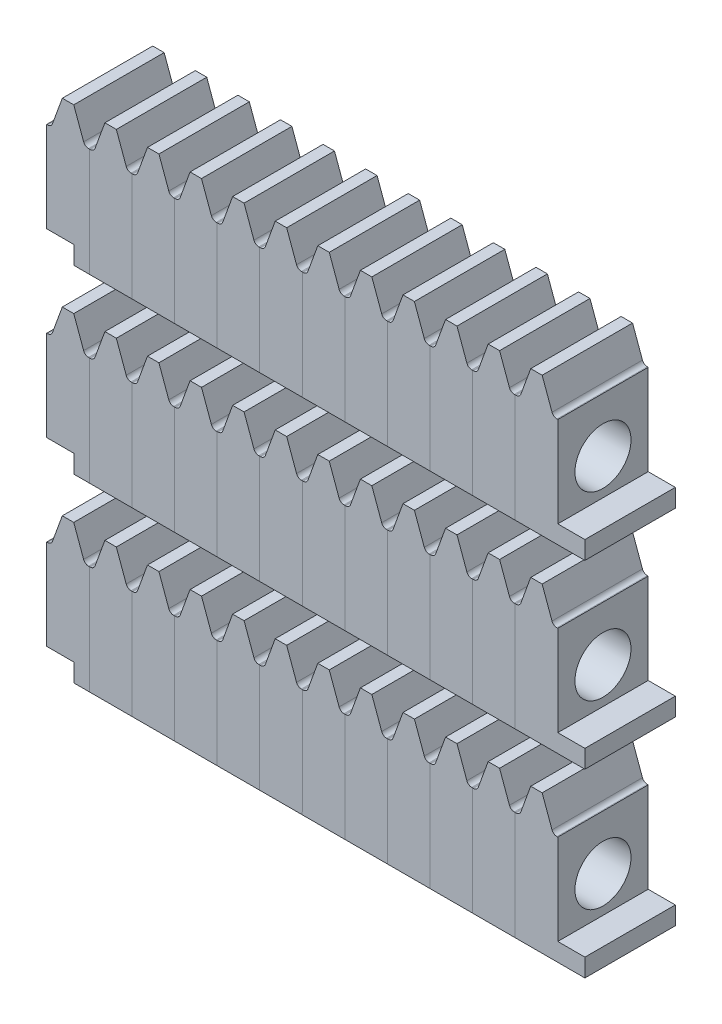
SolidWorks part; units mm, degrees
ref_plane "Front Plane" through (0, 0, 0) normal (0, 0, 1) x (1, 0, 0)
ref_plane "Top Plane" through (0, 0, 0) normal (0, 1, 0) x (1, 0, 0)
ref_plane "Right Plane" through (0, 0, 0) normal (1, 0, 0) x (0, 0, -1)
ref_axis "Axis1" through (0.1856, 0, 0) along (-1, 0, 0)
sketch "Sketch1" plane through (0, 0, 0) normal (0, 0, 1) x (1, 0, 0)
  line L0 (-3.7211, 0) -> (-2.4927, 3.375)
  line L1 (-2.4927, 3.375) -> (-1.2284, 3.375)
  line L2 (-1.2284, 3.375) -> (0, 0)
  line L3 (-3.7211, 0) -> (-4.7124, 0) construction
  line L4 (-3.7211, 0) -> (0, 0)
  line L5 (-3.5846, 0.375) -> (-4.8489, 0.375) construction
  line L6 (-4.7124, 0) -> (-5.3948, 1.875) construction
  line L7 (-5.3948, 1.875) -> (-0.6824, 1.875) construction
  dimension "D1" = 1.5
  dimension "D2" = 3.375
  dimension "D3" = 4.7124
  dimension "D4" = 3
  dimension "D5" = 70
  dimension "D6" = 0.9913
extrude "Main" add sketch "Sketch1" along normal blind 10
sketch "Sketch2" plane through (0, 0, 10) normal (0, 0, 1) x (1, 0, 0)
  line L1 (-4.2211, 0) -> (0.5, 0)
  line L2 (-4.2211, 0) -> (-4.2211, -12)
  line L3 (-4.2211, -12) -> (0.5, -12)
  line L4 (0.5, 0) -> (0.5, -12)
  line L6 (0.1856, 0) -> (-3.898, 0) construction
  point P12 (0, 0)
  dimension "D1" = 12
  dimension "D2" = 0.5
  dimension "D3" = 0.5
extrude "Support" add sketch "Sketch2" against normal up to surface (10 mm away) up to face at (-1.8605, 1.6875, 0)
sketch "Sketch3" plane through (-4.2211, 0, 0) normal (-1, 0, 0) x (0, 0, 1)
  line L0 (0, -12) -> (10, -12) construction
  line L1 (10, 0) -> (10, -12) construction
  circle A0 centre (5, -6) radius 3.1
  point P2 (5, -12)
  point P3 (10, -6)
  point P6 (0, 0)
  dimension "D1" = 6.2
extrude "AxisHole" cut sketch "Sketch3" against normal through all
fillet "Fillet1" radius 0.57 2 edges at (-3.7211, 0, 5) (0, 0, 5)
pattern_linear "LPattern2" count 12 spacing 4.71 along (-1, 0, 0) of bodies 112
sketch "Sketch4" plane through (0.5, 0, 0) normal (1, 0, 0) x (0, 0, -1)
  line L0 (-10, -12) -> (-10, 0) construction
  line L1 (-10, -10) -> (0, -10)
  line L2 (-10, -10) -> (-10, -12)
  line L3 (-10, -12) -> (0, -12)
  line L4 (0, -10) -> (0, -12)
  line L5 (0, -12) -> (-10, -12) construction
  line L6 (0, -12) -> (0, 0) construction
  dimension "D1" = 2
extrude "Boss-Extrude1" add sketch "Sketch4" along normal blind 3
sketch "Sketch5" plane through (-56.0311, 0, 0) normal (-1, 0, 0) x (0, 0, 1)
  line L0 (10, 0) -> (10, -12) construction
  line L1 (10, -10) -> (0, -10)
  line L2 (10, -10) -> (10, -12)
  line L3 (10, -12) -> (0, -12)
  line L4 (0, -10) -> (0, -12)
  point P4 (0, -10)
  point P6 (0, 0)
  point P7 (10, -8.692)
  dimension "D1" = 2
extrude "Cut-Extrude1" cut sketch "Sketch5" against normal blind 3
pattern_linear "LPattern3" count 3 spacing 20 along (0, -1, 0) of bodies 146 126 121 120 119 118 117 116 115 114 113 145
